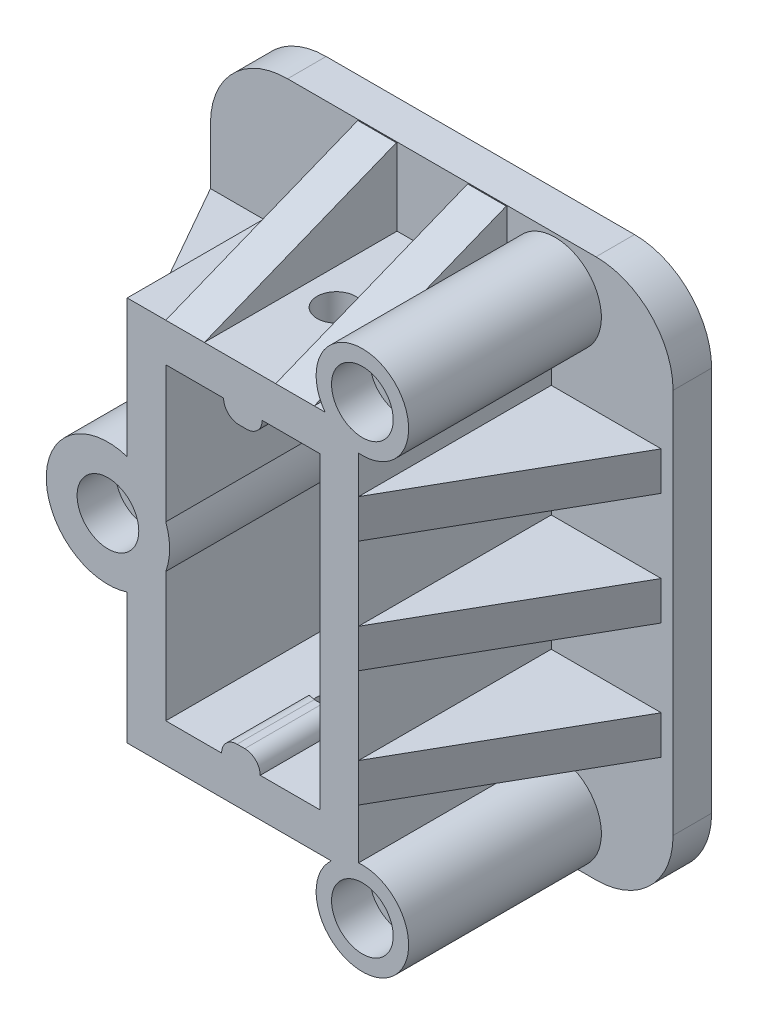
SolidWorks part; units mm, degrees
ref_plane "Front Plane" through (0, 0, 0) normal (0, 0, 1) x (1, 0, 0)
ref_plane "Top Plane" through (0, 0, 0) normal (0, 1, 0) x (1, 0, 0)
ref_plane "Right Plane" through (0, 0, 0) normal (1, 0, 0) x (0, 0, -1)
sketch "Sketch1" plane through (0, 0, 0) normal (0, 0, 1) x (1, 0, 0)
  line L1 (-33.6392, 54.6196) -> (6.3608, 54.6196)
  line L2 (-43.6392, 44.6196) -> (-43.6392, -5.3804)
  line L3 (-33.6392, -15.3804) -> (6.3608, -15.3804)
  line L4 (16.3608, 44.6196) -> (16.3608, -5.3804)
  circle A0 centre (1.0613, 48.1599) radius 2.5
  circle A2 centre (1.0613, -9.8401) radius 2.5
  circle A3 centre (-31.9387, 19.1599) radius 2.5
  arc A4 (6.3608, -15.3804) -> (16.3608, -5.3804) centre (6.3608, -5.3804) ccw
  arc A5 (-43.6392, -5.3804) -> (-33.6392, -15.3804) centre (-33.6392, -5.3804) ccw
  arc A6 (-33.6392, 54.6196) -> (-43.6392, 44.6196) centre (-33.6392, 44.6196) ccw
  arc A7 (6.3608, 54.6196) -> (16.3608, 44.6196) centre (6.3608, 44.6196) cw
  dimension "D3" = 5
  dimension "D4" = 10
  dimension "D1" = 60
  dimension "D2" = 70
extrude "Boss-Extrude1" add sketch "Sketch1" along normal blind 5
sketch "Sketch3" plane through (0, 0, 5) normal (0, 0, 1) x (1, 0, 0)
  line L0 (-33.6392, -15.3804) -> (6.3608, -15.3804) construction
  line L1 (-24.4387, 39.6004) -> (-4.4387, 39.6004)
  line L2 (-24.4387, 39.6004) -> (-24.4387, -0.3996)
  line L3 (-24.4387, -0.3996) -> (-4.4387, -0.3996)
  line L4 (-4.4387, 39.6004) -> (-4.4387, -0.3996)
  line L5 (-29.4387, 44.6004) -> (-24.4387, 44.6004)
  line L6 (-29.4387, 44.6004) -> (-29.4387, 37.282)
  line L7 (-29.4387, -5.3996) -> (-24.4387, -5.3996)
  line L8 (0.5613, 44.6004) -> (0.5613, 37.282)
  line L9 (0.5613, 37.282) -> (14.8252, 37.282)
  line L10 (-29.4387, 32.282) -> (-29.4387, 7.6373)
  line L11 (0.5613, 32.282) -> (14.8252, 32.282)
  line L12 (14.8252, 37.282) -> (14.8252, 32.282)
  line L13 (0.5613, 22.7197) -> (14.8252, 22.7197)
  line L14 (0.5613, 32.282) -> (0.5613, 22.7197)
  line L15 (0.5613, 17.7197) -> (14.8252, 17.7197)
  line L16 (14.8252, 22.7197) -> (14.8252, 17.7197)
  line L17 (0.5613, 7.6373) -> (14.8252, 7.6373)
  line L18 (0.5613, 17.7197) -> (0.5613, 7.6373)
  line L19 (0.5613, 2.6373) -> (14.8252, 2.6373)
  line L20 (14.8252, 7.6373) -> (14.8252, 2.6373)
  line L21 (-29.4387, 2.6373) -> (-43.7027, 2.6373)
  line L22 (-43.7027, 7.6373) -> (-43.7027, 2.6373)
  line L23 (-29.4387, 7.6373) -> (-43.7027, 7.6373)
  line L24 (-29.4387, 32.282) -> (-43.7027, 32.282)
  line L25 (-43.7027, 37.282) -> (-43.7027, 32.282)
  line L26 (-29.4387, 37.282) -> (-43.7027, 37.282)
  line L28 (-24.4387, -5.3996) -> (-24.4387, -15.3804)
  line L29 (-24.4387, -15.3804) -> (-19.4387, -15.3804)
  line L30 (-19.4387, -5.3996) -> (-19.4387, -15.3804)
  line L31 (0.5613, 2.6373) -> (0.5613, -5.3996)
  line L32 (-19.4387, -5.3996) -> (-10.1846, -5.3996)
  line L33 (-10.1846, -5.3996) -> (-10.1846, -15.3804)
  line L34 (-10.1846, -15.3804) -> (-5.1846, -15.3804)
  line L35 (-5.1846, -5.3996) -> (-5.1846, -15.3804)
  line L36 (-29.4387, 2.6373) -> (-29.4387, -5.3996)
  line L37 (-24.4387, -15.3804) -> (-19.4387, -15.3804)
  line L38 (-10.1846, -15.3804) -> (-5.1846, -15.3804)
  line L39 (-19.4387, 44.6004) -> (-10.1846, 44.6004)
  line L40 (-10.1846, 44.6004) -> (-10.1846, 54.5813)
  line L41 (-5.1846, 44.6004) -> (-5.1846, 54.5813)
  line L42 (-10.1846, 54.5813) -> (-5.1846, 54.5813)
  line L43 (-24.4387, 54.5813) -> (-19.4387, 54.5813)
  line L44 (-24.4387, 44.6004) -> (-24.4387, 54.5813)
  line L45 (-19.4387, 44.6004) -> (-19.4387, 54.5813)
  line L46 (-5.1846, 44.6004) -> (0.5613, 44.6004)
  line L47 (-5.1846, -5.3996) -> (0.5613, -5.3996)
  line M7 (-43.6392, 44.6196) -> (-43.6392, -5.3804)
  line M9 (-33.6392, -15.3804) -> (6.3608, -15.3804)
  dimension "D1" = 40
  dimension "D2" = 20
  dimension "D3" = 50
  dimension "D4" = 30
  dimension "D5" = 5
  dimension "D6" = 5
  dimension "D7" = 5
  dimension "D8" = 5
  dimension "D9" = 5
  dimension "D10" = 5
  dimension "D11" = 5
extrude "Boss-Extrude5" add sketch "Sketch3" along normal blind 25 contours L35 L47 L31 L19 L20 L17 L18 L15 L16 L13 L14 L11 L12 L9 L8 L46 L41 L42 L40 L39 L45 L43 L44 L5 L6 L26 L24 L10 L23 L21 L36 L7 L28 L30 L32 L33 L1 L4 L3 L2 M7 M9
sketch "Sketch5" plane through (0, 2.6373, 0) normal (0, -1, 0) x (1, 0, 0)
  line L0 (-43.6392, 5) -> (-29.4387, 30)
  line L1 (-29.4387, 30) -> (0.5613, 30)
  line L2 (0.5613, 30) -> (14.8252, 5)
extrude "Cut-Extrude2" cut sketch "Sketch5" along direction (0, 1, 0) on the side against the normal through all and the other way through all
sketch "Sketch7" plane through (-24.4387, 0, 0) normal (-1, 0, 0) x (0, 0, 1)
  line L0 (30, 44.6004) -> (5, 54.6196)
  line L1 (5, -15.3804) -> (30, -5.3996)
extrude "Cut-Extrude-Thin13" cut sketch "Sketch7" against normal through all thin
sketch "Sketch8" plane through (0, 39.6004, 0) normal (0, -1, 0) x (1, 0, 0)
  line L0 (-24.4387, 30) -> (-4.4387, 30) construction
  line L1 (-16.9387, 30) -> (-11.9387, 30)
  line L2 (-16.9387, 30) -> (-16.9387, 5)
  line L3 (-16.9387, 5) -> (-11.9387, 5)
  line L4 (-11.9387, 30) -> (-11.9387, 5)
  line L5 (-24.4387, 5) -> (-4.4387, 5) construction
  dimension "D1" = 5
  dimension "D3" = 5
extrude "Boss-Extrude6" add sketch "Sketch8" along normal blind 2
fillet "Fillet3" radius 2 2 edges at (-16.9387, 37.6004, 17.5) (-11.9387, 37.6004, 17.5)
sketch "Sketch9" plane through (0, -0.3996, 0) normal (0, 1, 0) x (1, 0, 0)
  line L0 (-24.4387, -5) -> (-4.4387, -5) construction
  line L1 (-17.1905, -5) -> (-12.1905, -5)
  line L2 (-17.1905, -5) -> (-17.1905, -30)
  line L3 (-17.1905, -30) -> (-12.1905, -30)
  line L4 (-12.1905, -5) -> (-12.1905, -30)
  line L5 (-24.4387, -30) -> (-4.4387, -30) construction
  dimension "D1" = 5
extrude "Boss-Extrude7" add sketch "Sketch9" along normal blind 2
fillet "Fillet4" radius 2 2 edges at (-12.1905, 1.6004, 17.5) (-17.1905, 1.6004, 17.5)
sketch "Sketch11" plane through (0, 0, 30) normal (0, 0, 1) x (1, 0, 0)
  circle A0 centre (-31.9387, 19.1599) radius 4.5
extrude "Cut-Extrude4" cut sketch "Sketch11" along a picked direction on the side against the normal blind 25
sketch "Sketch12" plane through (0, 0, 5) normal (0, 0, 1) x (1, 0, 0)
  circle A0 centre (1.0613, 48.1599) radius 6
  circle A1 centre (1.0613, -9.8401) radius 6
  circle A2 centre (-31.9387, 19.1599) radius 8
extrude "Boss-Extrude8" add sketch "Sketch12" along normal blind 25
sketch "Sketch13" plane through (0, 0, 0) normal (0, 0, -1) x (-1, 0, 0)
  circle A0 centre (31.9387, 19.1599) radius 2.5
  circle A1 centre (-1.0613, -9.8401) radius 2.5
  circle A2 centre (-1.0613, 48.1599) radius 2.5
extrude "Cut-Extrude5" cut sketch "Sketch13" against normal blind 28
sketch "Sketch14" plane through (0, 0, 30) normal (0, 0, 1) x (1, 0, 0)
  circle A0 centre (-31.9387, 19.1599) radius 4
  circle A1 centre (1.0613, 48.1599) radius 4
  circle A2 centre (1.0613, -9.8401) radius 4
extrude "Cut-Extrude6" cut sketch "Sketch14" against normal blind 5
sketch "Sketch15" plane through (0, 44.6004, 0) normal (0, 1, 0) x (1, 0, 0)
  line L0 (-29.4387, -17.5) -> (-8.6483, -17.5)
  line L1 (-29.4387, -30) -> (-29.4387, -5) construction
  line L2 (-14.8117, -30) -> (-14.8117, -5)
  line L3 (-19.4387, -30) -> (-10.1846, -30) construction
  line L4 (-19.4387, -5) -> (-10.1846, -5) construction
  circle A0 centre (-14.8117, -17.5) radius 2.5
extrude "Cut-Extrude7" cut sketch "Sketch15" against normal blind 70 and the other way blind 18 contours A0
